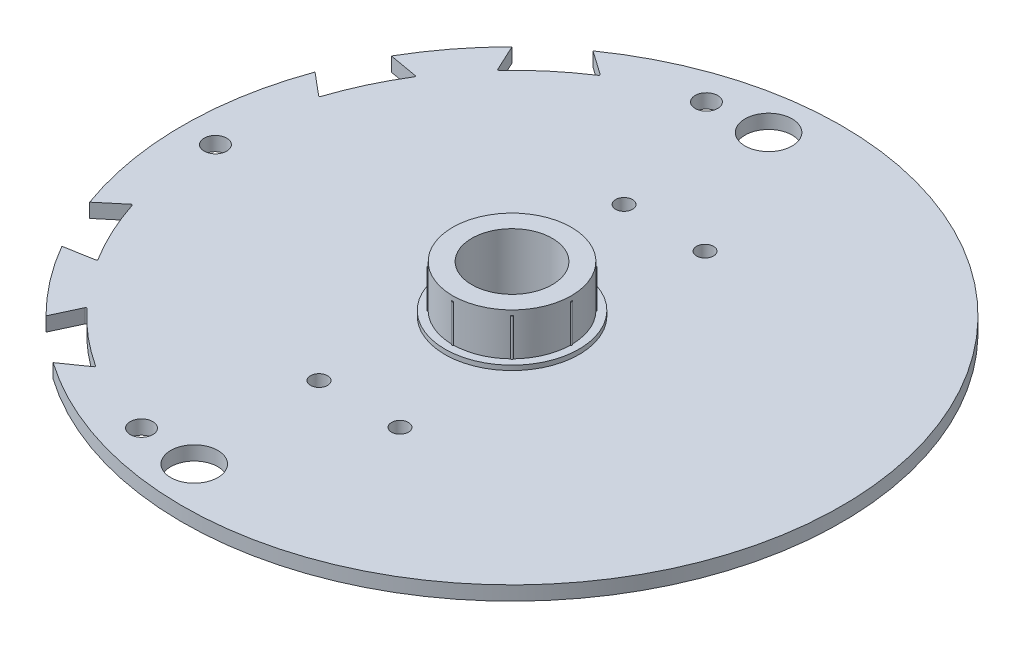
SolidWorks part; units mm, degrees
ref_plane "Front Plane" through (0, 0, 0) normal (0, 0, 1) x (1, 0, 0)
ref_plane "Top Plane" through (0, 0, 0) normal (0, 1, 0) x (1, 0, 0)
ref_plane "Right Plane" through (0, 0, 0) normal (1, 0, 0) x (0, 0, -1)
sketch "Sketch1" plane through (0, 0, 0) normal (0, 1, 0) x (1, 0, 0)
  circle A0 centre (0, 0) radius 70
  dimension "D1" = 140
extrude "base-plate" add sketch "Sketch1" along normal blind 3
sketch "Sketch2" plane through (0, 3, 0) normal (0, 1, 0) x (1, 0, 0)
  circle A0 centre (0, 0) radius 14.25
  dimension "D1" = 28.5
extrude "bearing-stepup" add sketch "Sketch2" along normal blind 1
sketch "Sketch3" plane through (0, 4, 0) normal (0, 1, 0) x (1, 0, 0)
  circle A0 centre (0, 0) radius 12.6
  dimension "D1" = 25.2
extrude "bearing-sitting" add sketch "Sketch3" along normal blind 9
sketch "Sketch4" plane through (0, 4, 0) normal (0, 1, 0) x (1, 0, 0)
  circle A0 centre (0, 12.6) radius 0.2
  circle A1 centre (0, 0) radius 12.6 construction
  circle A2 centre (0, 0) radius 12.6 construction
  circle A3 centre (8.9095, 8.9095) radius 0.2
  circle A4 centre (12.6, 0) radius 0.2
  circle A5 centre (8.9095, -8.9095) radius 0.2
  circle A6 centre (0, -12.6) radius 0.2
  circle A7 centre (-8.9095, -8.9095) radius 0.2
  circle A8 centre (-12.6, 0) radius 0.2
  circle A9 centre (-8.9095, 8.9095) radius 0.2
  point P23 (0, 0)
  dimension "D1" = 0.4
  dimension "D2" = 8
extrude "bearing-sitting-grid" add sketch "Sketch4" along normal blind 8
sketch "Sketch5" plane through (0, 0, 0) normal (0, -1, 0) x (1, 0, 0)
  line L2 (7.15, 0) -> (-7.15, 0) construction
  circle A0 centre (-18.7, 60) radius 2.4
  circle A1 centre (-63, 0) radius 2.4
  circle A2 centre (-18.7, -60) radius 2.4
  dimension "D3" = 4.8
  dimension "D4" = 4.8
  dimension "D1" = 63
  dimension "D2" = 60
  dimension "D5" = 18.7
extrude "m4-screw-clearance-holes" cut sketch "Sketch5" against normal through all contours A0 | A1 | A2 region at (-18.7, 0, 60) region at (-63, 0, 0)
sketch "Sketch6" plane through (0, 0, 0) normal (0, -1, 0) x (1, 0, 0)
  line L0 (7.15, 0) -> (-7.15, 0) construction
  circle A0 centre (-6.5, 61) radius 5
  circle A1 centre (-6.5, -61) radius 5
  dimension "D3" = 10
  dimension "D1" = 61
  dimension "D2" = 6.5
extrude "holes-reserved-for-rods" cut sketch "Sketch6" against normal through all
sketch "Sketch8" plane through (0, 13, 0) normal (0, 1, 0) x (1, 0, 0)
  circle A0 centre (0, 0) radius 8.55
  dimension "D1" = 17.1
extrude "Cut-Extrude1" cut sketch "Sketch8" against normal through all
sketch "Sketch9" plane through (0, 3, 0) normal (0, 1, 0) x (1, 0, 0)
  line L0 (0, -7.15) -> (0, 7.15) construction
  line L1 (-7.15, 0) -> (7.15, 0) construction
  circle A0 centre (-8.6, 32.4) radius 1.8
  circle A1 centre (8.6, 32.4) radius 1.8
  circle A2 centre (8.6, -32.4) radius 1.8
  circle A3 centre (-8.6, -32.4) radius 1.8
  dimension "D1" = 3.6
  dimension "D2" = 8.6
  dimension "D3" = 32.4
extrude "Cut-Extrude2" cut sketch "Sketch9" against normal up to next
sketch "Sketch10" plane through (0, 3, 0) normal (0, 1, 0) x (1, 0, 0)
  line L0 (-34.9731, 53.5993) -> (-40.2333, 57.2825)
  line L1 (-46.712, 43.7492) -> (-49.4258, 49.569)
  line L2 (-49.4258, 49.569) -> (-40.2333, 57.2825) construction
  line L3 (-7.15, 0) -> (7.15, 0) construction
  line L6 (-44.8295, 53.4258) -> (0, 0) construction
  line L7 (0, 0) -> (0, 21.039) construction
  line L8 (-35.0368, 53.7659) -> (-40.2333, 57.4046)
  line L9 (-46.865, 43.8408) -> (-49.5461, 49.5903)
  line L10 (-54.4765, 33.9213) -> (-60.724, 35.0229)
  line L11 (-61.0021, 19.9273) -> (-65.8617, 24.005)
  line L12 (0, 0) -> (-34.7944, 53.5962) construction
  line L13 (0, 0) -> (-54.1852, 33.8699) construction
  line L14 (-46.74, 43.5727) -> (-49.5461, 49.5903) construction
  line L15 (-34.7944, 53.5962) -> (-40.2333, 57.4046) construction
  line L16 (-61.0021, -19.9273) -> (-65.8617, -24.005)
  line L17 (-54.4765, -33.9213) -> (-60.724, -35.0229)
  line L18 (-46.865, -43.8408) -> (-49.5461, -49.5903)
  line L19 (-35.0368, -53.7659) -> (-40.2333, -57.4046)
  circle A1 centre (0, 0) radius 70 construction
  arc A2 (-34.9731, 53.5993) -> (-46.712, 43.7492) centre (0, 0) ccw
  arc A5 (-40.2333, 57.4046) -> (-49.5461, 49.5903) centre (0, 0) ccw
  arc A6 (-35.0418, 53.4348) -> (-46.5381, 43.7883) centre (0, 0) ccw
  arc A7 (-60.724, 35.0229) -> (-65.8617, 24.005) centre (0, 0) ccw
  arc A8 (-54.3412, 33.6191) -> (-60.6836, 20.0178) centre (0, 0) ccw
  arc A9 (-40.2333, 57.2825) -> (-49.4258, 49.569) centre (0, 0) ccw construction
  arc A10 (-61.0021, 19.9273) -> (-60.6836, 20.0178) centre (-60.8735, 20.0805) ccw
  arc A11 (-54.4765, 33.9213) -> (-54.3412, 33.6191) centre (-54.5113, 33.7243) cw
  arc A12 (-34.7944, 53.5962) -> (-46.74, 43.5727) centre (0, 0) ccw construction
  arc A13 (-46.865, 43.8408) -> (-46.5381, 43.7883) centre (-46.6838, 43.9253) ccw
  arc A14 (-35.0368, 53.7659) -> (-35.0418, 53.4348) centre (-35.1515, 53.6021) cw
  arc A15 (-35.0368, -53.7659) -> (-35.0418, -53.4348) centre (-35.1515, -53.6021) ccw
  arc A16 (-46.865, -43.8408) -> (-46.5381, -43.7883) centre (-46.6838, -43.9253) cw
  arc A17 (-54.4765, -33.9213) -> (-54.3412, -33.6191) centre (-54.5113, -33.7243) ccw
  arc A18 (-61.0021, -19.9273) -> (-60.6836, -20.0178) centre (-60.8735, -20.0805) cw
  arc A19 (-54.3412, -33.6191) -> (-60.6836, -20.0178) centre (0, 0) cw
  arc A20 (-60.724, -35.0229) -> (-65.8617, -24.005) centre (0, 0) cw
  arc A21 (-35.0418, -53.4348) -> (-46.5381, -43.7883) centre (0, 0) cw
  arc A22 (-40.2333, -57.4046) -> (-49.5461, -49.5903) centre (0, 0) cw
  point P30 (-54.1852, 33.8699)
  circle M14 centre (0, 0) radius 70
  dimension "D3" = 64
  dimension "D4" = 40
  dimension "D9" = 0.2
  dimension "D1" = 105
  dimension "D2" = 105
  dimension "D5" = 12
  dimension "D8" = 25
  dimension "D6" = 0.1
  dimension "D7" = 2
extrude "Cut-Extrude3" cut sketch "Sketch10" against normal through all contours A6 L8 L0 A2 L1 L9 M14 | A2 L0 L1 M14 | L8 A5 L9 M14 | A8 L10 L11 M14 | L10 A7 L11 M14 | A17 A19 A18 L16 L17 M14 | A20 L17 L16 M14 | A15 A21 A16 L18 L19 M14 | A22 L19 L18 M14 region at (-42.9118, 3, -51.1403) region at (-37.5918, 3, -55.4572) region at (-45.003, 3, -53.6325) region at (-63.4527, 3, -29.5885) region at (-60.4544, 3, -28.1903) region at (-42.8765, 3, 51.0983) region at (-40.2602, 3, 57.2735) region at (-63.4527, 3, 29.5885) region at (-60.4544, 3, 28.1903)
